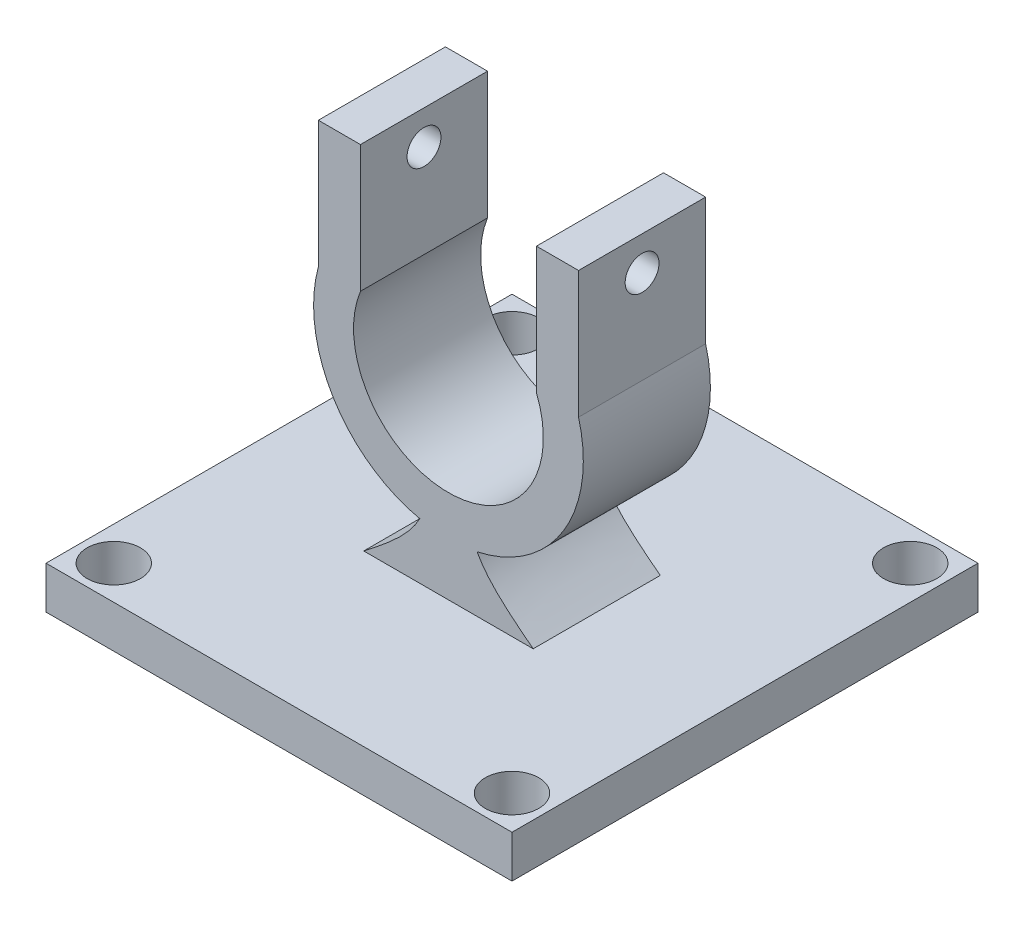
SolidWorks part; units mm, degrees
ref_plane "Front Plane" through (0, 0, 0) normal (0, 0, 1) x (1, 0, 0)
ref_plane "Top Plane" through (0, 0, 0) normal (0, 1, 0) x (1, 0, 0)
ref_plane "Right Plane" through (0, 0, 0) normal (1, 0, 0) x (0, 0, -1)
sketch "Sketch1" plane through (0, 0, 0) normal (0, 1, 0) x (1, 0, 0)
  line L1 (-27.5, 27.5) -> (27.5, 27.5)
  line L2 (-27.5, 27.5) -> (-27.5, -27.5)
  line L3 (-27.5, -27.5) -> (27.5, -27.5)
  line L4 (27.5, 27.5) -> (27.5, -27.5)
  line L5 (-27.5, 27.5) -> (27.5, -27.5) construction
  line L6 (-27.5, -27.5) -> (27.5, 27.5) construction
  point P0 (0, 0)
  dimension "D1" = 55
  dimension "D2" = 55
extrude "Boss-Extrude1" add sketch "Sketch1" along normal blind 5
sketch "Sketch2" plane through (0, 5, 0) normal (0, 1, 0) x (1, 0, 0)
  line L1 (-10, 7.5) -> (10, 7.5)
  line L2 (-10, 7.5) -> (-10, -7.5)
  line L3 (-10, -7.5) -> (10, -7.5)
  line L4 (10, 7.5) -> (10, -7.5)
  line L5 (-10, 7.5) -> (10, -7.5) construction
  line L6 (-10, -7.5) -> (10, 7.5) construction
  point P0 (0, 0)
  dimension "D1" = 20
  dimension "D2" = 15
ref_plane "Plane1" through (0, 15, 0) normal (0, 1, 0) x (1, 0, 0)
sketch "Sketch3" plane through (0, 15, 0) normal (0, 1, 0) x (1, 0, 0)
  line L0 (-10, -7.5) -> (10, -7.5) construction
  line L1 (-2.5, 7.5) -> (2.5, 7.5)
  line L2 (-2.5, 7.5) -> (-2.5, -7.5)
  line L3 (-2.5, -7.5) -> (2.5, -7.5)
  line L4 (2.5, 7.5) -> (2.5, -7.5)
  line L5 (-2.5, 7.5) -> (2.5, -7.5) construction
  line L6 (-2.5, -7.5) -> (2.5, 7.5) construction
  point P0 (0, 0)
  dimension "D1" = 5
loft "Loft1" add profiles "Sketch3", "Sketch2" start constraint normal to profile start tangent length 1 connector at (-2.5, 15, -7.5) connector at (-10, 5, -7.5)
sketch "Sketch7" plane through (0, 0, 0) normal (0, -1, 0) x (-1, 0, 0)
  line L0 (27.5, 27.5) -> (27.5, -27.5) construction
  line L1 (27.5, -27.5) -> (-27.5, -27.5) construction
  line L2 (-27.5, -27.5) -> (-27.5, 27.5) construction
  line L3 (-27.5, 27.5) -> (27.5, 27.5) construction
  circle A0 centre (23.5, -23.5) radius 3.15
  circle A1 centre (-23.5, -23.5) radius 3.15
  circle A2 centre (-23.5, 23.5) radius 3.15
  circle A3 centre (23.5, 23.5) radius 3.15
  dimension "D1" = 6.3
  dimension "D2" = 6.3
  dimension "D3" = 6.3
  dimension "D4" = 6.3
  dimension "D5" = 4
  dimension "D6" = 4
  dimension "D7" = 4
  dimension "D8" = 4
  dimension "D9" = 4
  dimension "D10" = 4
  dimension "D11" = 4
  dimension "D12" = 4
extrude "Cut-Extrude1" cut sketch "Sketch7" against normal through all
sketch "Sketch8" plane through (0, 0, -7.5) normal (0, 0, -1) x (-1, 0, 0)
  line L0 (0, 8.0817) -> (0, 29.8134) construction
  line L1 (-10.3863, 31.3495) -> (-10.3863, 46.3495)
  line L3 (10.3863, 31.3495) -> (10.3863, 46.3495)
  line L4 (15.355, 31.3495) -> (-15.355, 31.3495) construction
  line L6 (-15.355, 31.3495) -> (-15.355, 46.3495)
  line L7 (15.355, 31.3495) -> (15.355, 46.3495)
  line L8 (-15.355, 46.3495) -> (-10.3863, 46.3495)
  line L9 (10.3863, 46.3495) -> (15.355, 46.3495)
  arc A0 (-15.355, 31.3495) -> (15.355, 31.3495) centre (0, 27.1585) ccw
  arc A1 (10.6664, 23.7426) -> (-10.6664, 23.7426) centre (0, 27.1585) cw
  arc A2 (-10.6664, 23.7426) -> (-11.1978, 26.9385) centre (0, 27.1585) cw
  arc A3 (10.6664, 23.7426) -> (11.1967, 27.4289) centre (0, 27.1585) ccw
  arc A4 (-15.355, 31.3495) -> (15.9162, 27.2784) centre (0, 27.1585) ccw
  arc A5 (-11.1978, 26.9385) -> (-10.3863, 31.3495) centre (0, 27.1585) cw
  arc A6 (11.1967, 27.4289) -> (10.3863, 31.3495) centre (0, 27.1585) ccw
  circle A7 centre (0, 27.1585) radius 11.2
  dimension "D1" = 11.2
  dimension "D2" = 15
  dimension "D3" = 15
  dimension "D4" = 4.9687
  dimension "D5" = 30.7101
extrude "Boss-Extrude2" add sketch "Sketch8" against normal blind 15 contours L6 L8 L1 A5 A2 A1 A3 A6 L3 L9 L7 A0
sketch "Sketch10" plane through (15.355, 0, 0) normal (1, 0, 0) x (0, 0, -1)
  line L0 (-7.5, 31.3495) -> (-7.5, 46.3495) construction
  line L2 (-7.5, 46.3495) -> (7.5, 46.3495) construction
  circle A0 centre (0, 42.3495) radius 2
  dimension "D1" = 4
  dimension "D3" = 4
  dimension "D2" = 7.5
extrude "Cut-Extrude2" cut sketch "Sketch10" against normal through all
